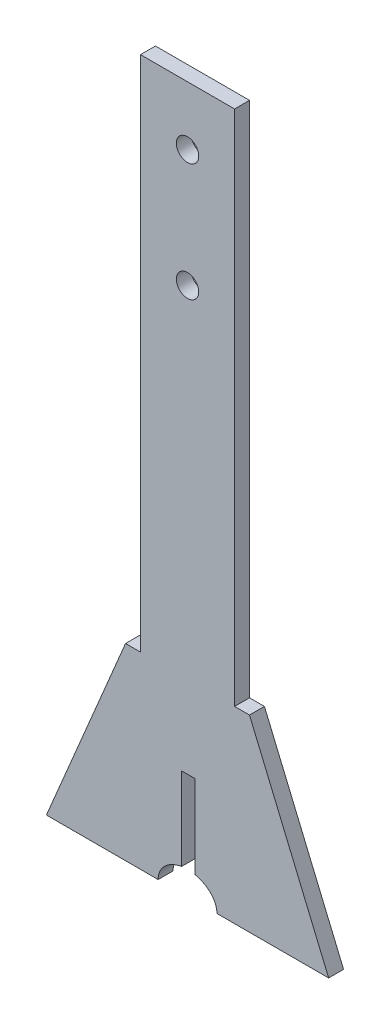
SolidWorks part; units mm, degrees
material "ABS"
ref_plane "Plan de face" through (0, 0, 0) normal (0, 0, 1) x (1, 0, 0)
ref_plane "Plan de dessus" through (0, 0, 0) normal (0, 1, 0) x (1, 0, 0)
ref_plane "Plan de droite" through (0, 0, 0) normal (1, 0, 0) x (0, 0, -1)
sketch "Esquisse1" plane through (0, 0, 0) normal (0, 0, 1) x (1, 0, 0)
  line L1 (-20, 300) -> (20, 300)
  line L2 (-20, 300) -> (-20, 80)
  line L4 (20, 300) -> (20, 80)
  line L8 (-60, 0) -> (60, 0)
  line L9 (26.35, 80) -> (-26.35, 80) construction
  line L10 (26.35, 80) -> (60, 0)
  line L11 (-26.35, 80) -> (-60, 0)
  line L12 (26.35, 80) -> (20, 80)
  line L13 (-20, 80) -> (-26.35, 80)
  point P1 (0, 0)
  point P2 (0, 300)
  point P8 (0, 80)
  dimension "D1" = 80
  dimension "D2" = 120
  dimension "D3" = 40
  dimension "D4" = 300
  dimension "D5" = 6.35
extrude "Boss.-Extru.1" add sketch "Esquisse1" along normal mid plane 6.35
sketch "Sketch1" plane through (0, 0, 3.175) normal (0, 0, 1) x (1, 0, 0)
  line L0 (20, 300) -> (-20, 300) construction
  circle A0 centre (0, 275) radius 4.7625
  circle A1 centre (0, 225) radius 4.7625
  point P6 (0, 300)
  dimension "D2" = 25
  dimension "D3" = 9.525
  dimension "D1" = 50
extrude "Cut-Extrude1" cut sketch "Sketch1" against normal up to surface (6.35 mm away) up to face at (0, 115, -3.175)
sketch "Esquisse2" plane through (0, 0, 3.175) normal (0, 0, 1) x (1, 0, 0)
  line L0 (-60, 0) -> (60, 0) construction
  line L1 (-12.5, 0) -> (12.5, 0)
  ellipse E0 centre (0, 0) end of major axis (12.5, 0) minor radius 10 (-12.5, 0) -> (12.5, 0) cw
  dimension "D1" = 10
  dimension "D2" = 25
extrude "Enlèv. mat.-Extru.1" cut sketch "Esquisse2" against normal up to surface (6.35 mm away) up to face at (-4.7625, 275, -3.175)
sketch "Esquisse3" plane through (0, 0, 3.175) normal (0, 0, 1) x (1, 0, 0)
  line L1 (-2.54, 45) -> (3.175, 45)
  line L2 (-2.54, 45) -> (-2.54, 0)
  line L3 (-2.54, 0) -> (3.175, 0)
  line L4 (3.175, 45) -> (3.175, 0)
  line L5 (-2.54, 43.6375) -> (-2.54, -57.9625) construction
  line L6 (3.175, -57.9625) -> (3.175, 43.6375) construction
  line L7 (-60, 0) -> (-12.5, 0) construction
  dimension "D1" = 0
  dimension "D2" = 45
extrude "Enlèv. mat.-Extru.2" cut sketch "Esquisse3" against normal up to surface (6.35 mm away) up to face at (0, 93, -3.175)
